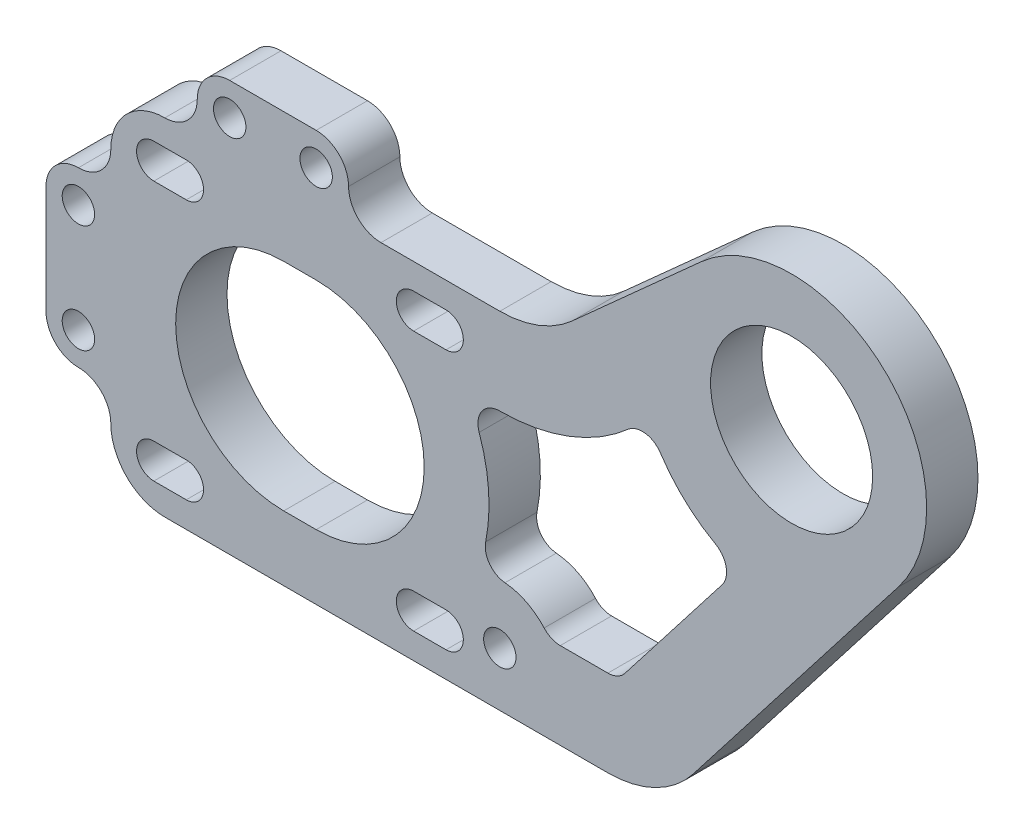
SolidWorks part; units mm, degrees
material "AISI Type A2 Tool Steel"
ref_plane "Front Plane" through (0, 0, 0) normal (0, 0, 1) x (1, 0, 0)
ref_plane "Top Plane" through (0, 0, 0) normal (0, 1, 0) x (1, 0, 0)
ref_plane "Right Plane" through (0, 0, 0) normal (1, 0, 0) x (0, 0, -1)
ref_axis "X" through (-88.99, 0, 0) along (1, 0, 0)
ref_axis "Y" through (0, 55, 0) along (0, -1, 0)
ref_axis "Z" through (0, 0, -88.99) along (0, 0, 1)
sketch "Sketch1" plane through (0, 0, 0) normal (0, 0, 1) x (1, 0, 0)
  line L0 (0, 0) -> (47, 0) construction
  line L1 (47, 0) -> (47, 20) construction
  line L2 (-16, 11) -> (-16, -11)
  line L3 (-11, -16) -> (30, -16)
  line L4 (37.9021, -12.1283) -> (56.8777, 12.3396)
  line L5 (-11, 16) -> (20, 16)
  line L6 (26.6796, 18.558) -> (38.6506, 29.3025)
  line L7 (0, 0) -> (47, 0) construction
  line L8 (47, 0) -> (47, 20) construction
  line L9 (20, 16) -> (20, 0) construction
  line L10 (30, -16) -> (30, 0) construction
  line L11 (0, 10) -> (3, 10)
  line L12 (3, -10) -> (0, -10)
  line L13 (-22, 5) -> (-22, -5)
  line L14 (-5, 22) -> (3, 22)
  line L15 (-19, 5) -> (-19, 8) construction
  line L16 (-19, 5) -> (-16, 5) construction
  line L17 (-8, 19) -> (-5, 19) construction
  line L18 (-5, 19) -> (-5, 16) construction
  line L19 (31.5804, -7.2257) -> (40.561, 4.3543)
  line L21 (31.8566, 12.4549) -> (32.0232, 12.6044)
  line L22 (20, 8) -> (19.9706, 8)
  line L23 (25.5902, -8) -> (30, -8)
  circle A0 centre (0, 0) radius 10
  circle A1 centre (47, 20) radius 7.5
  circle A2 centre (47, 20) radius 12.5
  circle A3 centre (0, 0) radius 16 construction
  arc A4 (-16, -11) -> (-11, -16) centre (-11, -11) ccw
  arc A5 (30, -16) -> (37.9021, -12.1283) centre (30, -6) ccw
  arc A6 (-16, 11) -> (-11, 16) centre (-11, 11) cw
  arc A7 (20, 16) -> (26.6796, 18.558) centre (20, 26) ccw
  arc A8 (3, 10) -> (3, -10) centre (3, 0) cw
  arc A9 (-16, 11) -> (-19, 8) centre (-19, 11) cw
  arc A10 (-19, 8) -> (-22, 5) centre (-19, 5) ccw
  arc A11 (-22, -5) -> (-19, -8) centre (-19, -5) ccw
  arc A12 (-19, -8) -> (-16, -11) centre (-19, -11) cw
  arc A13 (-11, 16) -> (-8, 19) centre (-11, 19) ccw
  arc A14 (-8, 19) -> (-5, 22) centre (-5, 19) cw
  arc A15 (3, 22) -> (6, 19) centre (3, 19) cw
  arc A16 (6, 19) -> (9, 16) centre (9, 19) ccw
  circle A17 centre (20, -11) radius 1.5
  circle A18 centre (-5, 19) radius 1.5
  circle A19 centre (3, 19) radius 1.5
  circle A20 centre (-19, -5) radius 1.5
  circle A21 centre (-19, 5) radius 1.5
  arc A22 (40.561, 4.3543) -> (39.9526, 7.3278) centre (38.9805, 5.5799) ccw
  arc A23 (39.9526, 7.3278) -> (34.8662, 12.0615) centre (47, 20) cw
  arc A24 (34.8662, 12.0615) -> (31.8566, 12.4549) centre (33.1926, 10.9665) ccw
  arc A26 (19.9706, 8) -> (18.0849, 5.3333) centre (19.9706, 6) ccw
  arc A27 (18.0849, 5.3333) -> (18.6896, -3.1363) centre (3, 0) cw
  arc A29 (30, -8) -> (31.5804, -7.2257) centre (30, -6) ccw
  arc A30 (32.0232, 12.6044) -> (20, 8) centre (20, 26) cw
  arc A31 (18.6896, -3.1363) -> (20.4773, -5.5207) centre (20.6508, -3.5283) ccw
  arc A32 (20.4773, -5.5207) -> (24.0995, -7.3333) centre (20, -11) cw
  arc A33 (24.0995, -7.3333) -> (25.5902, -8) centre (25.5902, -6) ccw
  point P71 (26.6796, -11.2033)
  point P72 (17.5524, -3.6371)
  point P73 (26.0799, -11)
  point P78 (17.4222, -4.2044)
  point P82 (24.9398, -10.5816)
  dimension "D1" = 20
  dimension "D2" = 32
  dimension "D3" = 5
  dimension "D4" = 5
  dimension "D5" = 15
  dimension "D8" = 10
  dimension "D6" = 3
  dimension "D10" = 5
  dimension "D11" = 3
  dimension "D12" = 3
  dimension "D13" = 10
  dimension "D16" = 2
  dimension "D17" = 8
  dimension "D18" = 2
  dimension "D19" = 8
  dimension "D20" = 6
  dimension "D21" = 4
  dimension "D7" = 20
  dimension "D9" = 30
  dimension "D14" = 8
  dimension "D15" = 10
extrude "Boss-Extrude1" add sketch "Sketch1" along normal mid plane 4.75 contours A7 L5 A6 L2 A4 L3 A5 L4 A2 L6 A0 | A2 A1 | A16 A15 L14 A14 A13 L5 A19 A18 | A11 A12 L2 A9 A10 L13 A21 A20 region at (14.3716, 0.6822, 0) region at (-18.7801, 0, 0) region at (-1, 18.7424, 0) region at (38.7251, 11.1083, 0)
sketch "Sketch2" plane through (0, 0, 0) normal (0, 0, 1) x (1, 0, 0)
  line L0 (-12.0208, 12.0208) -> (-9.0208, 12.0208) construction
  line L1 (-12.0208, 13.6208) -> (-9.0208, 13.6208)
  line L2 (-12.0208, 10.4208) -> (-9.0208, 10.4208)
  line L3 (12.0208, 12.0208) -> (15.0208, 12.0208) construction
  line L4 (12.0208, 13.6208) -> (15.0208, 13.6208)
  line L5 (12.0208, 10.4208) -> (15.0208, 10.4208)
  line L6 (-12.0208, -12.0208) -> (-9.0208, -12.0208) construction
  line L7 (-12.0208, -10.4208) -> (-9.0208, -10.4208)
  line L8 (-12.0208, -13.6208) -> (-9.0208, -13.6208)
  line L9 (12.0208, -12.0208) -> (15.0208, -12.0208) construction
  line L10 (12.0208, -10.4208) -> (15.0208, -10.4208)
  line L11 (12.0208, -13.6208) -> (15.0208, -13.6208)
  line L12 (-12.0208, 12.0208) -> (-12.0208, -12.0208) construction
  line L13 (-12.0208, -12.0208) -> (12.0208, -12.0208) construction
  line L14 (12.0208, -12.0208) -> (12.0208, 12.0208) construction
  line L15 (12.0208, 12.0208) -> (-12.0208, 12.0208) construction
  circle A0 centre (0, 0) radius 17 construction
  arc A1 (-12.0208, 13.6208) -> (-12.0208, 10.4208) centre (-12.0208, 12.0208) ccw
  arc A2 (-9.0208, 10.4208) -> (-9.0208, 13.6208) centre (-9.0208, 12.0208) ccw
  arc A3 (12.0208, 13.6208) -> (12.0208, 10.4208) centre (12.0208, 12.0208) ccw
  arc A4 (15.0208, 10.4208) -> (15.0208, 13.6208) centre (15.0208, 12.0208) ccw
  arc A5 (-12.0208, -10.4208) -> (-12.0208, -13.6208) centre (-12.0208, -12.0208) ccw
  arc A6 (-9.0208, -13.6208) -> (-9.0208, -10.4208) centre (-9.0208, -12.0208) ccw
  arc A7 (12.0208, -10.4208) -> (12.0208, -13.6208) centre (12.0208, -12.0208) ccw
  arc A8 (15.0208, -13.6208) -> (15.0208, -10.4208) centre (15.0208, -12.0208) ccw
  point P5 (-10.5208, 12.0208)
  point P12 (13.5208, 12.0208)
  point P17 (-10.5208, -12.0208)
  point P24 (13.5208, -12.0208)
  dimension "D1" = 34
  dimension "D2" = 1.6
  dimension "D3" = 3
extrude "Cut-Extrude1" cut sketch "Sketch2" against normal through all both and the other way through all
